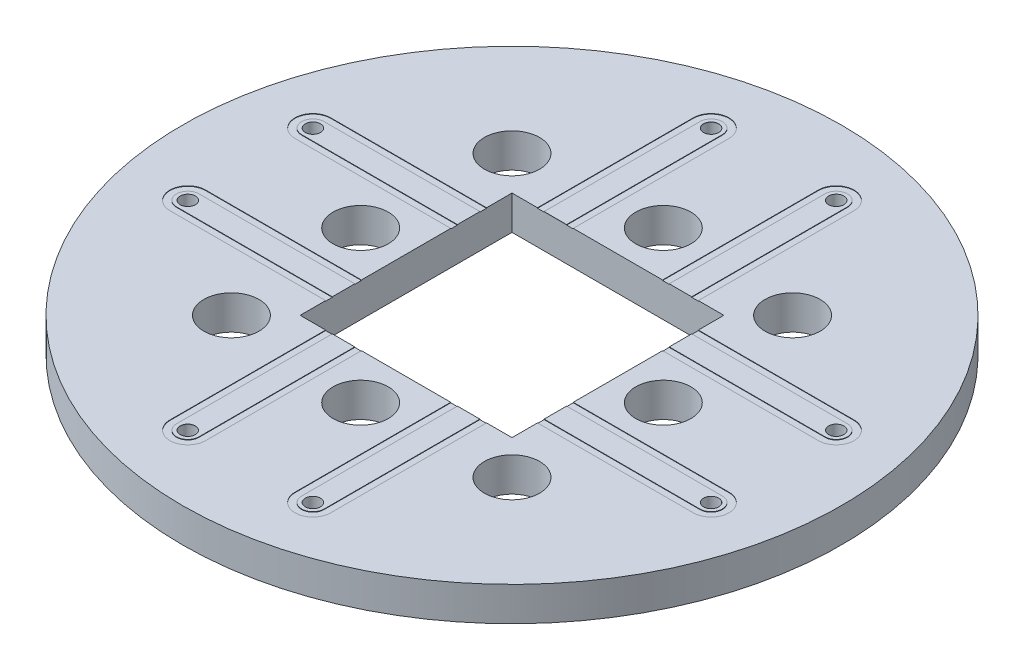
SolidWorks part; units mm, degrees
material "Ceramic Porcelain"
ref_plane "Front Plane" through (0, 0, 0) normal (0, 0, 1) x (1, 0, 0)
ref_plane "Top Plane" through (0, 0, 0) normal (0, 1, 0) x (1, 0, 0)
ref_plane "Right Plane" through (0, 0, 0) normal (1, 0, 0) x (0, 0, -1)
ref_axis "Y Axis" through (0, 0.0762, 0) along (0, -1, 0)
sketch "Body Sketch" plane through (0, 0, 0) normal (0, 1, 0) x (1, 0, 0)
  circle A0 centre (0, 0) radius 12.446
  dimension "D1" = 24.892
extrude "Body" add sketch "Body Sketch" against normal blind 1.27
sketch "Copper Sketch" plane through (0, 0, 0) normal (0, 1, 0) x (1, 0, 0)
  circle A0 centre (0, 0) radius 12.446
  dimension "D1" = 24.892
extrude "Copper" add sketch "Copper Sketch" along normal blind 0.0175
sketch "IO Hole Positions" plane through (0, 0, 0) normal (0, 1, 0) x (1, 0, 0)
  line L0 (-12.446, 0) -> (12.446, 0) construction
  circle A1 centre (0, 0) radius 12.446 construction
  point P1 (-2.3622, 9.8816)
  point P8 (-2.3622, -9.8816)
  dimension "D2" = 2.3622
sketch "Gap" plane through (0, 0, 0) normal (0, 1, 0) x (1, 0, 0)
  line L10 (-3.0372, 9.8816) -> (-3.0372, -9.8816)
  line L11 (-12.446, 0) -> (12.446, 0) construction
  line L12 (-3.0372, 0) -> (-1.6872, 0) construction
  line L13 (-1.6872, -9.8816) -> (-1.6872, 9.8816)
  arc A5 (-1.6872, 9.8816) -> (-3.0372, 9.8816) centre (-2.3622, 9.8816) ccw
  arc A6 (-1.6872, -9.8816) -> (-3.0372, -9.8816) centre (-2.3622, -9.8816) cw
  dimension "D1" = 0.675
sketch "Center Sketch" plane through (0, 0, 0) normal (0, 1, 0) x (1, 0, 0)
  line L6 (-2.7872, 9.8816) -> (-2.7872, -9.8816)
  line L7 (-12.446, 0) -> (12.446, 0) construction
  line L8 (-2.7872, 0) -> (-1.9372, 0) construction
  line L9 (-1.9372, -9.8816) -> (-1.9372, 9.8816)
  arc A3 (-1.9372, 9.8816) -> (-2.7872, 9.8816) centre (-2.3622, 9.8816) ccw
  arc A4 (-1.9372, -9.8816) -> (-2.7872, -9.8816) centre (-2.3622, -9.8816) cw
  dimension "D1" = 0.425
extrude "Gap Cut" cut sketch "Gap" along normal through all
extrude "Center" add sketch "Center Sketch" along normal blind 0.0175 separate body
sketch "IO Hole Sketch" plane through (0, 0, 0) normal (0, 1, 0) x (1, 0, 0)
  circle A1 centre (-2.3622, 9.8816) radius 0.287
  circle A3 centre (-2.3622, -9.8816) radius 0.287
  circle A4 centre (0, 0) radius 10.16 construction
  dimension "D1" = 0.574
  dimension "D2" = 0.574
  dimension "D3" = 20.32
  dimension "D4" = 2.3622
extrude "IO Hole" cut sketch "IO Hole Sketch" against normal through all and the other way through all
pattern_circular "Gap Cuts" count 4 over 360 about axis through (0, 0.0762, 0) along (0, -1, 0) of "Gap Cut"
pattern_circular "Centers" count 4 over 360 about axis through (0, 0.0762, 0) along (0, -1, 0) of "Center"
pattern_circular "IO Holes" count 4 over 360 about axis through (0, 0.0762, 0) along (0, -1, 0) of "IO Hole"
sketch "Pocket Sketch" plane through (0, 0, 0) normal (0, 1, 0) x (1, 0, 0)
  line L1 (-4, -4) -> (4, -4)
  line L2 (-4, -4) -> (-4, 4)
  line L3 (-4, 4) -> (4, 4)
  line L4 (4, -4) -> (4, 4)
  line L5 (-4, -4) -> (4, 4) construction
  line L6 (-4, 4) -> (4, -4) construction
  point P0 (0, 0)
  dimension "D1" = 8
  dimension "D2" = 8
extrude "Pocket" cut sketch "Pocket Sketch" against normal through all and the other way through all
sketch "Posts" plane through (0, 0, 0) normal (0, 1, 0) x (1, 0, 0)
  circle A0 centre (0, 5.715) radius 1.0414
  circle A8 centre (-5.2984, 5.2984) radius 1.0414
  point P0 (0, 5.715)
  point P4 (-5.2984, 5.2984)
  dimension "D2" = 2.0828
  dimension "D4" = 2.0828
  dimension "D1" = 5.715
  dimension "D3" = 7.493
  dimension "D5" = 5.715
extrude "Post Cut" cut sketch "Posts" against normal through all and the other way through all
pattern_circular "Post Cuts" count 4 over 360 about axis through (0, 0.0762, 0) along (0, -1, 0) of "Post Cut"
equation "\"dielectric_d\" = 0.98in"
equation "\"dieletric_h\"= 0.05in"
equation "\"D1@Body\" = \"dieletric_h\""
equation "\"screw_inner_r\"= 0.415in"
equation "\"io_r\"= 0.4in"
equation "\"io_hole_d\"= 0.574mm"
equation "\"W\"= 0.85mm"
equation "\"G\"= 0.25mm"
equation "\"copper_t\"= 17.5um"
equation "\"silicon_size\"= 8mm"
equation "\"D1@Center\" = \"copper_t\""
equation "\"D1@Copper\"=\"copper_t\""
equation "\"D1@Pocket Sketch\" = \"silicon_size\""
equation "\"D2@Pocket Sketch\" = \"silicon_size\""
equation "\"post_r1\"= 0.225in"
equation "\"post_r2\"= 0.295in"
equation "\"D1@Posts\"=\"post_r1\""
equation "\"post_hole_size\"= 0.082in"
equation "\"D2@Posts\"=\"post_hole_size\""
equation "\"D3@Posts\"=\"post_r2\""
equation "\"D4@Posts\"=\"post_hole_size\""
equation "\"io_x\"= 0.093in"
equation "\"D1@IO Hole Positions\"=\"io_r\""
equation "\"D2@IO Hole Positions\"=\"io_x\""
equation "\"D1@IO Hole Sketch\"=\"io_hole_d\""
equation "\"D2@IO Hole Sketch\"=\"io_hole_d\""
equation "\"D1@Gap\"= \"W\" / 2 + \"G\""
equation "\"D1@Center Sketch\"=\"W\" / 2"
equation "\"D5@Posts\"=\"post_r1\""
equation "\"D4@IO Hole Sketch\"=\"io_x\""
equation "\"D1@Body Sketch\" = \"dielectric_d\""
equation "\"D1@Copper Sketch\"=\"dielectric_d\""
equation "\"D1@Boday Sketch\" = \"dielectric_d\""
